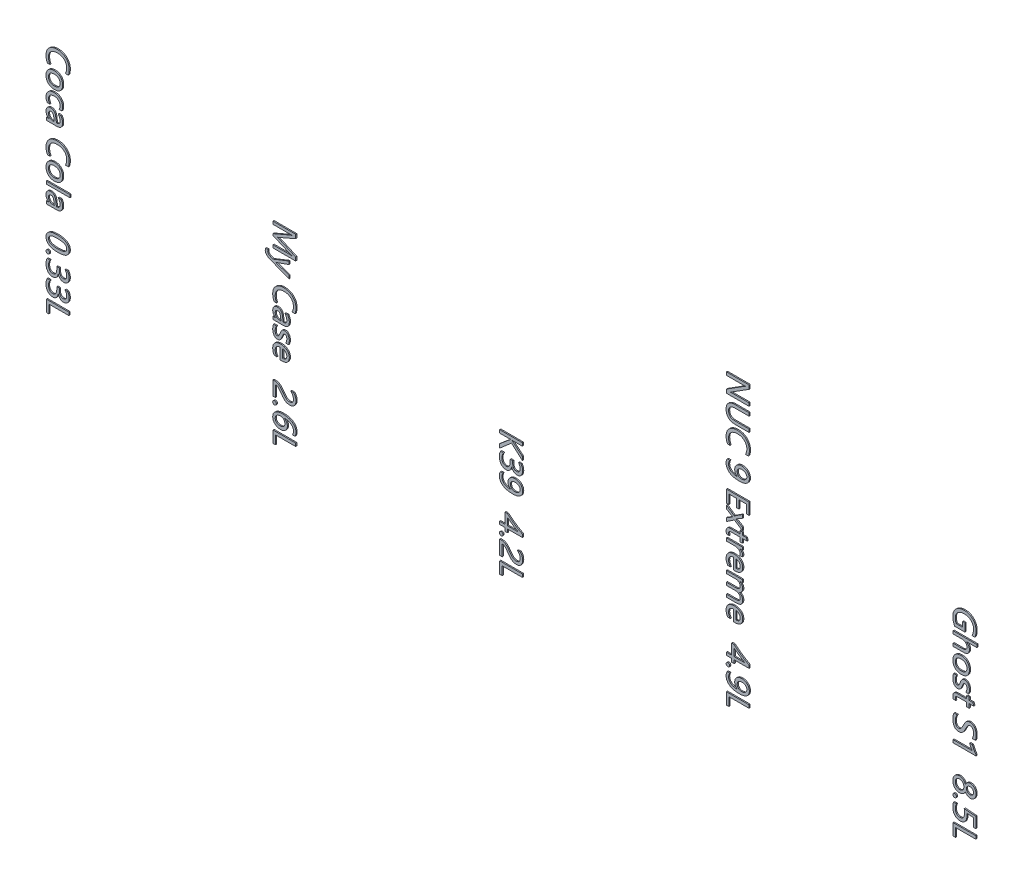
SolidWorks part; units mm, degrees
ref_plane "前视基准面" through (0, 0, 0) normal (0, 0, 1) x (1, 0, 0)
ref_plane "上视基准面" through (0, 0, 0) normal (0, 1, 0) x (1, 0, 0)
ref_plane "右视基准面" through (0, 0, 0) normal (1, 0, 0) x (0, 0, -1)
sketch "草图1" plane through (0, 0, 0) normal (0, 0, 1) x (1, 0, 0)
  line L0 (100, 0) -> (100, -649.4682) construction
  line L1 (0, 0) -> (1000, 0) construction
  line L2 (0, 0) -> (0, -200) construction
  line L3 (0, -200) -> (1000, -200) construction
  line L4 (1000, 0) -> (1000, -200) construction
  line L5 (300, 0) -> (300, -649.4682) construction
  line L6 (500, 0) -> (500, -649.4682) construction
  line L7 (700, 0) -> (700, -649.4682) construction
  line L8 (900, 0) -> (900, -649.4682) construction
  text T0 "Coca Cola  0.33L" font "@Microsoft YaHei UI" height 20
  text T1 "My Case  2.6L" font "@Microsoft YaHei UI" height 20
  text T2 "K39  4.2L" font "@Microsoft YaHei UI" height 20
  text T3 "NUC 9 Extreme  4.9L" font "@Microsoft YaHei UI" height 20
  text T4 "Ghost S1  8.5L" font "@Microsoft YaHei UI" height 20
  point P7 (100, -649.4682)
  dimension "D1" = 100
  dimension "D2" = 5
extrude "凸台-拉伸1" add sketch "草图1" along normal blind 1
